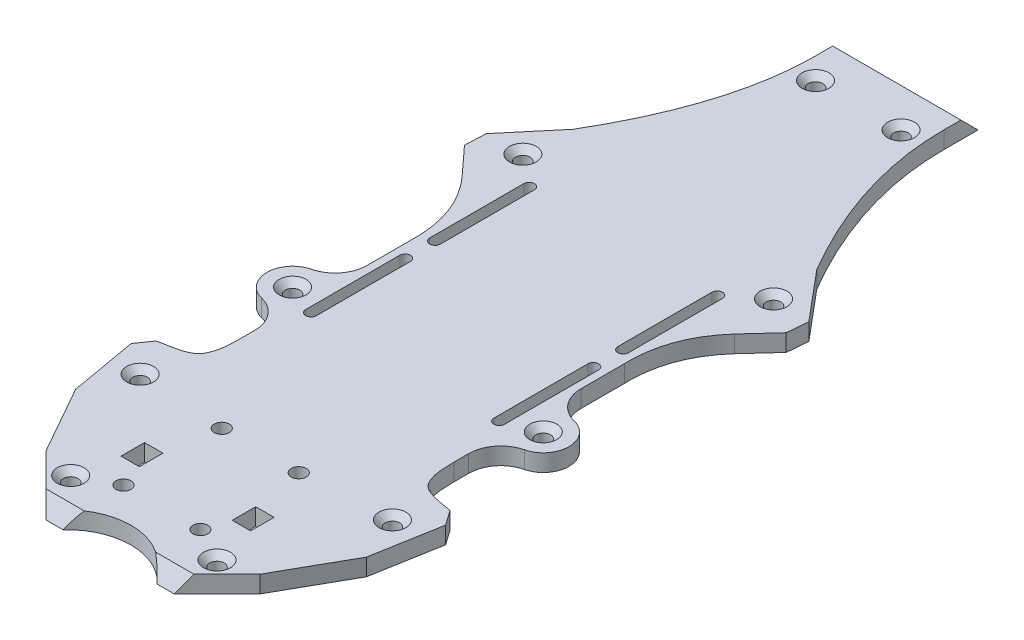
SolidWorks part; units mm, degrees
material "ABS PC"
ref_plane "Front Plane" through (0, 0, 0) normal (0, 0, 1) x (1, 0, 0)
ref_plane "Top Plane" through (0, 0, 0) normal (0, 1, 0) x (1, 0, 0)
ref_plane "Right Plane" through (0, 0, 0) normal (1, 0, 0) x (0, 0, -1)
sketch "Sketch1" plane through (0, 0, 0) normal (0, 1, 0) x (1, 0, 0)
  line L1 (25, -90) -> (-25, -90)
  line L2 (25, -90) -> (25, 90)
  line L3 (25, 90) -> (-25, 90)
  line L4 (-25, -90) -> (-25, 90)
  line L5 (25, -90) -> (-25, 90) construction
  line L6 (25, 90) -> (-25, -90) construction
  point P0 (0, 0)
  dimension "D1" = 50
  dimension "D2" = 180
extrude "Boss-Extrude1" add sketch "Sketch1" along normal blind 4
chamfer "Chamfer1" distance 10 angle 45 4 edges at (25, 2, 90) (-25, 2, 90) (-25, 2, -90) (25, 2, -90)
hole_wizard "CSK for M3 Flat Head Machine Screw1" positions "Sketch2" profile "Sketch3" countersink size "M3" standard "ANSI Metric" end condition through all
sketch "Sketch2" plane through (0, 4, 0) normal (0, 1, 0) x (1, 0, 0)
  line L0 (20, 0) -> (0, 0) construction
  line L3 (15, -90) -> (25, -80) construction
  line L4 (20, -85) -> (17.115, -82.115) construction
  line L6 (0, 14.9256) -> (0, -12.8781) construction
  point P0 (17.115, -82.115)
  point P24 (-17.115, -82.115)
  dimension "D2" = 4.08
sketch "Sketch3" plane through (17.115, 4, 82.115) normal (1, 0, 0) x (0, 0, 1)
  line L0 (0, 0) -> (0, 4)
  line L1 (0, 4) -> (1.7, 4)
  line L2 (1.7, 4) -> (1.7, 1.45)
  line L3 (1.7, 1.45) -> (3.15, 0)
  line L5 (3.15, 0) -> (0, 0)
  line L6 (-1.7, 1.45) -> (-3.15, 0) construction
  line L11 (0, -6.35) -> (0, 107.95) construction
  dimension "Thru Hole Dia." = 3.4
  dimension "Thru Hole Depth" = 4
  dimension "Near C'Sink Dia." = 6.3
  dimension "Near C'Sink Angle" = 90
hole_wizard "CSK for M3 Flat Head Machine Screw2" positions "Sketch6" profile "Sketch7" countersink size "M3" standard "ANSI Metric" end condition through all
sketch "Sketch6" plane through (0, 4, 0) normal (0, 1, 0) x (1, 0, 0)
  line L0 (0, 81.4101) -> (0, 72.2321) construction
  line L1 (15, 90) -> (-15, 90) construction
  point P5 (-10, 85)
  point P7 (10, 85)
  dimension "D1" = 20
  dimension "D2" = 5
sketch "Sketch7" plane through (10, 4, -85) normal (1, 0, 0) x (0, 0, 1)
  line L0 (0, 0) -> (0, 4)
  line L1 (0, 4) -> (1.7, 4)
  line L2 (1.7, 4) -> (1.7, 1.45)
  line L3 (1.7, 1.45) -> (3.15, 0)
  line L5 (3.15, 0) -> (0, 0)
  line L6 (-1.7, 1.45) -> (-3.15, 0) construction
  line L11 (0, -6.35) -> (0, 107.95) construction
  dimension "Thru Hole Dia." = 3.4
  dimension "Thru Hole Depth" = 4
  dimension "Near C'Sink Dia." = 6.3
  dimension "Near C'Sink Angle" = 90
sketch "Sketch8" plane through (0, 4, 0) normal (0, 1, 0) x (1, 0, 0)
  line L5 (0, -83.8452) -> (0, -79.2626) construction
  line L6 (10.85, -72.3) -> (15.15, -72.3)
  line L7 (10.85, -72.3) -> (10.85, -66.8)
  line L8 (10.85, -66.8) -> (15.15, -66.8)
  line L9 (15.15, -72.3) -> (15.15, -66.8)
  line L10 (-10.85, -66.8) -> (-15.15, -66.8)
  line L11 (-10.85, -72.3) -> (-10.85, -66.8)
  line L12 (-10.85, -72.3) -> (-15.15, -72.3)
  line L17 (-15.15, -66.8) -> (-15.15, -72.3)
  line L18 (-15, -90) -> (15, -90) construction
  dimension "D1" = 5.5
  dimension "D2" = 4.3
  dimension "D3" = 17.7
  dimension "D4" = 21.7
extrude "Cut-Extrude3" cut sketch "Sketch8" against normal through all
sketch "Sketch10" plane through (0, 4, 0) normal (0, 1, 0) x (1, 0, 0)
  line L0 (0, -52) -> (0, -79) construction
  line L1 (10, -79) -> (-10, -79) construction
  line L2 (10, -80) -> (-10, -80)
  line L3 (10, -78) -> (-10, -78)
  line L4 (0, -65.5) -> (3.454, -65.5) construction
  line L5 (10, -52) -> (-10, -52) construction
  line L6 (10, -51) -> (-10, -51)
  line L7 (10, -53) -> (-10, -53)
  line L8 (-15, -90) -> (15, -90) construction
  arc A0 (10, -80) -> (10, -78) centre (10, -79) ccw
  arc A1 (-10, -78) -> (-10, -80) centre (-10, -79) ccw
  arc A2 (10, -51) -> (10, -53) centre (10, -52) cw
  arc A3 (-10, -53) -> (-10, -51) centre (-10, -52) cw
  point P5 (0, -79)
  point P14 (0, -52)
  dimension "D1" = 20
  dimension "D2" = 2
  dimension "D3" = 25
  dimension "D4" = 10
extrude "Cut-Extrude6" [suppressed] cut sketch "Sketch10" against normal through all
sketch "Sketch12" plane through (0, 4, 0) normal (0, 1, 0) x (1, 0, 0)
  line L4 (19.07, -10) -> (22, -10) construction
  line L5 (22, -21) -> (22, 1) construction
  line L6 (20.75, -21) -> (20.75, 1)
  line L7 (23.25, -21) -> (23.25, 1)
  line L11 (20.75, -6.6772) -> (23.25, -6.6772) construction
  line L13 (25, -80) -> (25, 80) construction
  line L15 (22, -10) -> (25, -10) construction
  line L16 (0, 16.979) -> (0, -5.3504) construction
  line L17 (-22, -21) -> (-22, 1) construction
  line L18 (-20.75, -21) -> (-20.75, 1)
  line L19 (-23.25, -21) -> (-23.25, 1)
  line L23 (-22, -10) -> (-25, -10) construction
  line L26 (-20.75, -6.6772) -> (-23.25, -6.6772) construction
  line L27 (-19.07, -10) -> (-22, -10) construction
  line L33 (15, 90) -> (-15, 90) construction
  arc A0 (20.75, -21) -> (23.25, -21) centre (22, -21) ccw
  arc A1 (23.25, 1) -> (20.75, 1) centre (22, 1) ccw
  arc A4 (-20.75, -21) -> (-23.25, -21) centre (-22, -21) cw
  arc A5 (-23.25, 1) -> (-20.75, 1) centre (-22, 1) cw
  point P13 (22, -10)
  point P38 (-22, -10)
  dimension "D1" = 22
  dimension "D2" = 2.5
  dimension "D3" = 1.75
  dimension "D5" = 100
extrude "Cut-Extrude7" cut sketch "Sketch12" against normal through all
sketch "Sketch14" plane through (0, 4, 0) normal (0, 1, 0) x (1, 0, 0)
  line L0 (-15, -90) -> (15, -90) construction
  line L1 (0, -90) -> (0, -100) construction
  line L2 (-11, -90) -> (11, -90)
  arc A0 (-11, -90) -> (11, -90) centre (0, -100) cw
  dimension "D1" = 22
  dimension "D2" = 10
extrude "Cut-Extrude8" cut sketch "Sketch14" against normal through all
hole_wizard "Ø3.5 (3.5) Diameter Hole1" [suppressed] positions "Sketch16" profile "Sketch17" hole size "Ø3.5" standard "ANSI Metric"
sketch "Sketch16" plane through (0, 4, 0) normal (0, 1, 0) x (1, 0, 0)
  line L0 (0, 65) -> (0, -15) construction
  line L2 (20.75, 65) -> (0, 65) construction
  line L4 (15, 90) -> (-15, 90) construction
  point P0 (0, 65)
  point P2 (0, -15)
  dimension "D1" = 80
  dimension "D2" = 25
sketch "Sketch17" plane through (0, 4, -65) normal (1, 0, 0) x (0, 0, 1)
  line L0 (0, 0) -> (0, 4)
  line L1 (0, 4) -> (1.75, 4)
  line L2 (1.75, 4) -> (1.75, 0)
  line L5 (1.75, 0) -> (0, 0)
  line L11 (0, -6.35) -> (0, 107.95) construction
  dimension "Thru Hole Dia." = 3.5
  dimension "Thru Hole Depth" = 4
sketch "Sketch18" [suppressed] plane through (0, 0, 0) normal (0, -1, 0) x (1, 0, 0)
  line L1 (3.2332, 15) -> (1.6166, 17.8)
  line L2 (1.6166, 17.8) -> (-1.6166, 17.8)
  line L3 (-1.6166, 17.8) -> (-3.2332, 15)
  line L4 (-3.2332, 15) -> (-1.6166, 12.2)
  line L5 (-1.6166, 12.2) -> (1.6166, 12.2)
  line L6 (1.6166, 12.2) -> (3.2332, 15)
  line L7 (1.1033, -61.9609) -> (-2.0803, -62.5249)
  line L8 (-2.0803, -62.5249) -> (-3.1836, -65.564)
  line L9 (-3.1836, -65.564) -> (-1.1033, -68.0391)
  line L10 (-1.1033, -68.0391) -> (2.0803, -67.4751)
  line L11 (2.0803, -67.4751) -> (3.1836, -64.436)
  line L12 (3.1836, -64.436) -> (1.1033, -61.9609)
  circle A0 centre (0, 15) radius 2.8 construction
  circle A1 centre (0, -65) radius 2.8 construction
  dimension "D1" = 5.6
extrude "Cut-Extrude9" [suppressed] cut sketch "Sketch18" against normal blind 2
chamfer "Chamfer2" [suppressed] distance 2 angle 45
sketch "Sketch22" plane through (0, 4, 0) normal (0, 1, 0) x (1, 0, 0)
  line L0 (0, 30.3924) -> (0, 20.2286) construction
  line L19 (40, 33.07) -> (31.85, 24.1745)
  line L20 (31.85, 24.1745) -> (25, 5.3542)
  line L21 (25, 59.6542) -> (25, 5.3542)
  line L22 (28.4288, 46.8579) -> (40, 33.07)
  line L23 (28.4288, 46.8579) -> (25, 59.6542)
  line L24 (25, -80) -> (25, 80) construction
  line L25 (15, 90) -> (-15, 90) construction
  line L26 (-28.4288, 46.8579) -> (-25, 59.6542)
  line L27 (-28.4288, 46.8579) -> (-40, 33.07)
  line L28 (-25, 59.6542) -> (-25, 5.3542)
  line L29 (-31.85, 24.1745) -> (-25, 5.3542)
  line L30 (-40, 33.07) -> (-31.85, 24.1745)
  dimension "D1" = 20
  dimension "D2" = 6.85
  dimension "D3" = 18
  dimension "D4" = 15
  dimension "D5" = 15
  dimension "D6" = 56.93
  dimension "D7" = 54.3
  dimension "D8" = 97.5
extrude "Boss-Extrude4" add sketch "Sketch22" against normal through all
sketch "Sketch25" plane through (0, 4, 0) normal (0, 1, 0) x (1, 0, 0)
  line L0 (25, -43.1813) -> (25, -80)
  line L1 (25, -80) -> (25, 5.3542) construction
  line L3 (34, -64.0613) -> (37.2993, -45.35)
  line L4 (37.2993, -45.35) -> (25, -43.1813)
  line L5 (0, -64.3813) -> (0, -71.3505) construction
  line L6 (-37.2993, -45.35) -> (-25, -43.1813)
  line L7 (-34, -64.0613) -> (-37.2993, -45.35)
  line L8 (-25, -80) -> (-34, -64.0613)
  line L9 (-25, -43.1813) -> (-25, -80)
  line L11 (25, -80) -> (34, -64.0613)
  line L12 (11, -90) -> (15, -90) construction
  dimension "D1" = 10
  dimension "D2" = 9
  dimension "D3" = 19
  dimension "D4" = 44.65
extrude "Boss-Extrude5" add sketch "Sketch25" against normal through all
hole_wizard "CSK for M3 Flat Head Machine Screw3" positions "Sketch26" profile "Sketch27" countersink size "M3" standard "ANSI Metric" end condition through all
sketch "Sketch26" plane through (0, 4, 0) normal (0, 1, 0) x (1, 0, 0)
  point P0 (29.5085, -53.473)
  point P3 (-29.5085, -53.473)
  point P6 (29.3209, 35.8558)
  point P9 (-29.3209, 35.8558)
sketch "Sketch27" plane through (29.5085, 4, 53.473) normal (1, 0, 0) x (0, 0, 1)
  line L0 (0, 0) -> (0, 4)
  line L1 (0, 4) -> (1.7, 4)
  line L2 (1.7, 4) -> (1.7, 1.45)
  line L3 (1.7, 1.45) -> (3.15, 0)
  line L5 (3.15, 0) -> (0, 0)
  line L6 (-1.7, 1.45) -> (-3.15, 0) construction
  line L11 (0, -6.35) -> (0, 107.95) construction
  dimension "Thru Hole Dia." = 3.4
  dimension "Thru Hole Depth" = 4
  dimension "Near C'Sink Dia." = 6.3
  dimension "Near C'Sink Angle" = 90
chamfer "Chamfer6" distance 7 angle 45 2 edges at (-25, 2, 43.1813) (25, 2, 43.1813)
sketch "Sketch28" plane through (0, 4, 0) normal (0, 1, 0) x (1, 0, 0)
  line L0 (25, 59.6542) -> (15, 90)
  line L1 (15, 90) -> (25, 80)
  line L2 (25, 80) -> (25, 59.6542)
  line L3 (0, 45.2094) -> (0, 53.5542) construction
  line L4 (-25, 80) -> (-25, 59.6542)
  line L5 (-15, 90) -> (-25, 80)
  line L6 (-25, 59.6542) -> (-15, 90)
extrude "Cut-Extrude10" cut sketch "Sketch28" against normal through all
chamfer "Chamfer7" distance 3 angle 45 4 edges at (-37.2993, 2, 45.35) (37.2993, 2, 45.35) (40, 2, -33.07) (-40, 2, -33.07)
sketch "Sketch29" plane through (0, 4, 0) normal (0, 1, 0) x (1, 0, 0)
  line L0 (15, 90) -> (25, 59.6542)
  line L1 (25, 59.6542) -> (28.4288, 46.8579)
  line L2 (15, 90) -> (28.4288, 46.8579) construction
  line L3 (18.8499, 67.5373) -> (21.7144, 68.429) construction
  line L4 (0, 55.6435) -> (0, 44.7763) construction
  line L5 (-25, 59.6542) -> (-28.4288, 46.8579)
  line L6 (-15, 90) -> (-25, 59.6542)
  line L7 (15, 90) -> (-15, 90) construction
  spline S0 degree 3 poles (28.4288, 46.8579) (20.7903, 59.906) (15, 74.5743) (15, 90) knots 0 0 0 0 1 1 1 1
  spline S1 degree 3 poles (-28.4288, 46.8579) (-20.7903, 59.906) (-15, 74.5743) (-15, 90) knots 0 0 0 0 1 1 1 1
  dimension "D1" = 3
extrude "Cut-Extrude11" cut sketch "Sketch29" against normal through all
sketch "Sketch30" plane through (0, 4, 0) normal (0, 1, 0) x (1, 0, 0)
  line L0 (0, 16.644) -> (0, 25.7551) construction
  line L1 (31.85, 24.1745) -> (25, 5.3542)
  line L2 (-31.85, 24.1745) -> (-25, 5.3542)
  line L3 (28.425, 14.7644) -> (26.5456, 15.4484) construction
  spline S0 degree 2 poles (25, 5.3542) (24.6662, 16.1324) (31.85, 24.1745) knots 0 0 0 1 1 1
  spline S1 degree 2 poles (-25, 5.3542) (-24.6662, 16.1324) (-31.85, 24.1745) knots 0 0 0 1 1 1
  dimension "D1" = 2
extrude "Cut-Extrude12" cut sketch "Sketch30" against normal through all
sketch "Sketch31" plane through (0, 4, 0) normal (0, 1, 0) x (1, 0, 0)
  line L0 (0, -54.7209) -> (0, -42.6648) construction
  line L1 (25, -34.5517) -> (31.8937, -44.3968)
  line L2 (-25, -34.5517) -> (-31.8937, -44.3968)
  line L3 (28.4468, -39.4743) -> (25.9894, -41.195) construction
  line L4 (31.8937, -44.3968) -> (25, -34.5517) construction
  line L5 (25, -34.5517) -> (25, 5.3542) construction
  line L6 (34.3449, -44.8291) -> (31.8937, -44.3968) construction
  spline S0 degree 3 poles (25, -34.5517) (25, -38.2701) (25.7415, -41.4461) (27.4745, -43.6176) (31.8937, -44.3968) knots 0 0 0 0 0.5 1 1 1 1
  spline S1 degree 3 poles (-25, -34.5517) (-25, -38.2701) (-25.7415, -41.4461) (-27.4745, -43.6176) (-31.8937, -44.3968) knots 0 0 0 0 0.5 1 1 1 1
  dimension "D1" = 3
extrude "Cut-Extrude13" cut sketch "Sketch31" against normal through all
hole_wizard "Ø3.5 (3.5) Diameter Hole2" [suppressed] positions "Sketch33" profile "Sketch34" hole size "Ø3.5" standard "ANSI Metric"
sketch "Sketch33" plane through (0, 4, 0) normal (0, 1, 0) x (1, 0, 0)
  line L1 (-9, -77) -> (9, -77)
  line L2 (-9, -77) -> (-9, -54)
  line L3 (-9, -54) -> (9, -54)
  line L4 (9, -77) -> (9, -54)
  line L5 (-9, -77) -> (9, -54) construction
  line L6 (-9, -54) -> (9, -77) construction
  line L7 (0, 0) -> (0, -65.5) construction
  line L9 (-15, -90) -> (-11, -90) construction
  point P2 (9, -54)
  point P5 (-9, -77)
  point P6 (-9, -54)
  point P7 (9, -77)
  dimension "D1" = 18
  dimension "D2" = 23
  dimension "D3" = 13
sketch "Sketch34" plane through (9, 4, 54) normal (1, 0, 0) x (0, 0, 1)
  line L0 (0, 0) -> (0, 4)
  line L1 (0, 4) -> (1.75, 4)
  line L2 (1.75, 4) -> (1.75, 0)
  line L5 (1.75, 0) -> (0, 0)
  line L11 (0, -6.35) -> (0, 107.95) construction
  dimension "Thru Hole Dia." = 3.5
  dimension "Thru Hole Depth" = 4
sketch "Sketch35" plane through (0, 4, 0) normal (0, 1, 0) x (1, 0, 0)
  line L0 (29.3209, 35.8558) -> (29.3209, -18.0042) construction
  line L1 (29.3209, -12.0042) -> (25, -12.0042)
  line L2 (25, -34.5517) -> (25, 5.3542) construction
  line L3 (25, -12.0042) -> (25, -13.8413)
  line L4 (29.3209, -24.0042) -> (25, -24.0042)
  line L5 (25, -24.0042) -> (25, -22.1672)
  line L6 (0, -26.7981) -> (0, -19.6204) construction
  line L7 (-25, -24.0042) -> (-25, -22.1672)
  line L8 (-29.3209, -24.0042) -> (-25, -24.0042)
  line L9 (-25, -12.0042) -> (-25, -13.8413)
  line L10 (-29.3209, -12.0042) -> (-25, -12.0042)
  circle A0 centre (29.3209, -18.0042) radius 6
  circle A1 centre (-29.3209, -18.0042) radius 6
  dimension "D2" = 12
  dimension "D1" = 53.86
extrude "Boss-Extrude6" add sketch "Sketch35" against normal through all contours A1 | L10 A1 L9 | L7 A1 L8 | A0 | A0 L1 L3 | A0 L5 L4
fillet "Fillet1" radius 7.5 4 edges at (-25, 2, 12.0042) (-25, 2, 24.0042) (25, 2, 24.0042) (25, 2, 12.0042)
hole_wizard "CSK for M3 Flat Head Machine Screw4" positions "Sketch36" profile "Sketch37" countersink size "M3" standard "ANSI Metric" end condition through all
sketch "Sketch36" plane through (0, 4, 0) normal (0, 1, 0) x (1, 0, 0)
  point P0 (29.3209, -18.0042)
  point P3 (-29.3209, -18.0042)
sketch "Sketch37" plane through (29.3209, 4, 18.0042) normal (1, 0, 0) x (0, 0, 1)
  line L0 (0, 0) -> (0, 4)
  line L1 (0, 4) -> (1.7, 4)
  line L2 (1.7, 4) -> (1.7, 1.45)
  line L3 (1.7, 1.45) -> (3.15, 0)
  line L5 (3.15, 0) -> (0, 0)
  line L6 (-1.7, 1.45) -> (-3.15, 0) construction
  line L11 (0, -6.35) -> (0, 107.95) construction
  dimension "Thru Hole Dia." = 3.4
  dimension "Thru Hole Depth" = 4
  dimension "Near C'Sink Dia." = 6.3
  dimension "Near C'Sink Angle" = 90
sketch "Sketch38" plane through (0, 4, 0) normal (0, 1, 0) x (1, 0, 0)
  line L1 (-15, 90) -> (15, 90)
  line L2 (-15, 90) -> (-15, 98)
  line L3 (-15, 98) -> (15, 98)
  line L4 (15, 90) -> (15, 98)
  dimension "D1" = 8
extrude "Boss-Extrude7" add sketch "Sketch38" against normal through all
sketch "Sketch39" plane through (0, 4, 0) normal (0, 1, 0) x (1, 0, 0)
  line L0 (-10.85, -66.8) -> (-15.15, -66.8) construction
  line L1 (-15.15, -66.8) -> (-10.85, -66.8)
  line L2 (-15.15, -66.8) -> (-15.15, -72.3)
  line L3 (-15.15, -72.3) -> (-10.85, -72.3)
  line L4 (-10.85, -66.8) -> (-10.85, -72.3)
  line L6 (10.85, -66.8) -> (15.15, -66.8)
  line L7 (10.85, -66.8) -> (10.85, -72.3)
  line L8 (10.85, -72.3) -> (15.15, -72.3)
  line L9 (15.15, -66.8) -> (15.15, -72.3)
extrude "Boss-Extrude8" [suppressed] add sketch "Sketch39" against normal blind 1
chamfer "Chamfer8" distance 4 angle 45 1 edges at (0, 4, -98)
chamfer "Chamfer9" distance 4 angle 30 2 edges at (13, 4, 90) (-13, 4, 90)
sketch "Sketch41" plane through (0, 4, 0) normal (0, 1, 0) x (1, 0, 0)
  line L0 (23.25, -21) -> (23.25, 1) construction
  line L5 (22, 8) -> (22, 30) construction
  line L6 (20.75, 8) -> (20.75, 30)
  line L7 (23.25, 8) -> (23.25, 30)
  line L11 (20.75, 28.4426) -> (23.25, 28.4426) construction
  line L16 (0, 52.0988) -> (0, 29.7694) construction
  line L17 (-22, 8) -> (-22, 30) construction
  line L18 (-20.75, 8) -> (-20.75, 30)
  line L19 (-23.25, 8) -> (-23.25, 30)
  line L26 (-20.75, 28.4426) -> (-23.25, 28.4426) construction
  arc A0 (20.75, 8) -> (23.25, 8) centre (22, 8) ccw
  arc A1 (23.25, 30) -> (20.75, 30) centre (22, 30) ccw
  arc A4 (-20.75, 8) -> (-23.25, 8) centre (-22, 8) cw
  arc A5 (-23.25, 30) -> (-20.75, 30) centre (-22, 30) cw
  point P13 (22, 19)
  point P38 (-22, 19)
  dimension "D1" = 22
  dimension "D2" = 2.5
  dimension "D3" = 7
extrude "Cut-Extrude14" cut sketch "Sketch41" against normal through all
hole_wizard "Ø3.5 (3.5) Diameter Hole3" positions "Sketch42" profile "Sketch43" hole size "Ø3.5" standard "ANSI Metric" end condition through all
sketch "Sketch42" plane through (0, 4, 0) normal (0, 1, 0) x (1, 0, 0)
  line L0 (0, -58.2201) -> (0, -70.3081) construction
  point P0 (-9, -54.8856)
  point P2 (-9, -77.8856)
  point P9 (0, 0)
  point P10 (9, -77.8856)
  point P11 (9, -54.8856)
  dimension "D1" = 23
  dimension "D2" = 18
sketch "Sketch43" plane through (-9, 4, 54.8856) normal (1, 0, 0) x (0, 0, 1)
  line L0 (0, 0) -> (0, 4)
  line L1 (0, 4) -> (1.75, 4)
  line L2 (1.75, 4) -> (1.75, 0)
  line L5 (1.75, 0) -> (0, 0)
  line L11 (0, -6.35) -> (0, 107.95) construction
  dimension "Thru Hole Dia." = 3.5
  dimension "Thru Hole Depth" = 4
